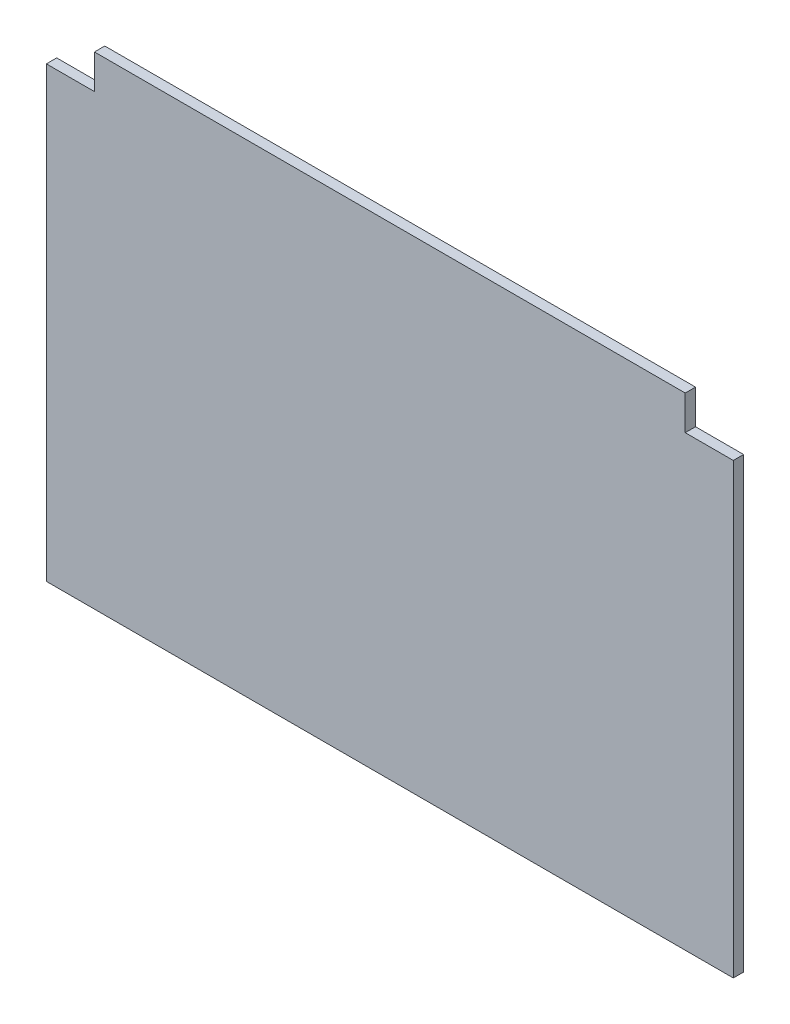
SolidWorks part; units mm, degrees
material "PET"
ref_plane "Front Plane" through (0, 0, 0) normal (0, 0, 1) x (1, 0, 0)
ref_plane "Top Plane" through (0, 0, 0) normal (0, 1, 0) x (1, 0, 0)
ref_plane "Right Plane" through (0, 0, 0) normal (1, 0, 0) x (0, 0, -1)
sketch "Sketch1" plane through (0, 0, 0) normal (0, 0, 1) x (1, 0, 0)
  line L1 (-28.5714, 258.1048) -> (371.4286, 258.1048)
  line L2 (-28.5714, 258.1048) -> (-28.5714, -22.8952)
  line L3 (-28.5714, -22.8952) -> (371.4286, -22.8952)
  line L4 (371.4286, 258.1048) -> (371.4286, -22.8952)
  dimension "D1" = 281
  dimension "D2" = 400
extrude "Boss-Extrude1" add sketch "Sketch1" along normal blind 6
sketch "Sketch2" plane through (0, 0, 6) normal (0, 0, 1) x (1, 0, 0)
  line L1 (-28.5714, 258.1048) -> (-0.5714, 258.1048)
  line L2 (-28.5714, 258.1048) -> (-28.5714, 238.1048)
  line L3 (-28.5714, 238.1048) -> (-0.5714, 238.1048)
  line L4 (-0.5714, 258.1048) -> (-0.5714, 238.1048)
  line L5 (371.4286, 258.1048) -> (343.4286, 258.1048)
  line L6 (371.4286, 258.1048) -> (371.4286, 238.1048)
  line L7 (371.4286, 238.1048) -> (343.4286, 238.1048)
  line L8 (343.4286, 258.1048) -> (343.4286, 238.1048)
  dimension "D1" = 20
  dimension "D2" = 20
  dimension "D3" = 28
  dimension "D4" = 28
extrude "Cut-Extrude1" cut sketch "Sketch2" against normal blind 10
